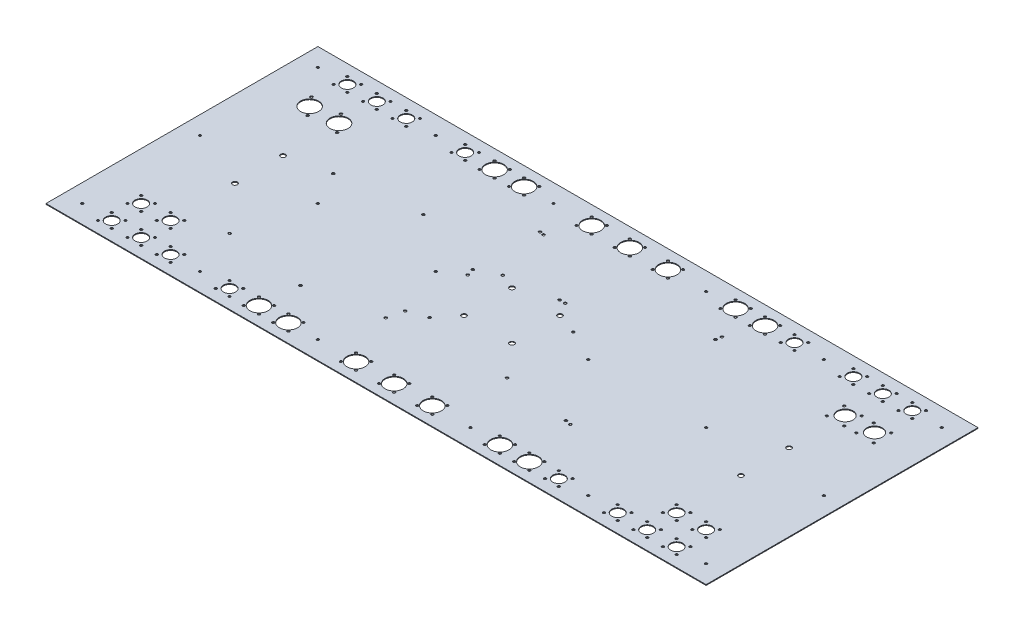
SolidWorks part; units mm, degrees
ref_plane "Front Plane" through (0, 0, 0) normal (0, 0, 1) x (1, 0, 0)
ref_plane "Top Plane" through (0, 0, 0) normal (0, 1, 0) x (1, 0, 0)
ref_plane "Right Plane" through (0, 0, 0) normal (1, 0, 0) x (0, 0, -1)
sketch "main_plate" plane through (0, 0, 0) normal (0, 1, 0) x (1, 0, 0)
  line L1 (-437, 180) -> (437, 180)
  line L2 (-437, 180) -> (-437, -180)
  line L3 (-437, -180) -> (437, -180)
  line L4 (437, 180) -> (437, -180)
  line L5 (-437, 180) -> (437, -180) construction
  line L6 (-437, -180) -> (437, 180) construction
  point P0 (0, 0)
  dimension "D1" = 360
  dimension "D2" = 874
extrude "Boss-Extrude1" add sketch "main_plate" along normal blind 1.016
sketch "main_holes" plane through (0, 1.016, 0) normal (0, 1, 0) x (1, 0, 0)
  line L0 (-437, 180) -> (-437, -180) construction
  line L1 (437, 180) -> (-437, 180) construction
  line L2 (-437, 0) -> (437, 0) construction
  line L3 (437, -180) -> (437, 180) construction
  line L4 (-437, -180) -> (437, -180) construction
  line L5 (0, 180) -> (0, -180) construction
  circle A0 centre (-413, 156) radius 1.6
  circle A3 centre (-335, 31.8059) radius 3.175
  circle A4 centre (-335, -31.8059) radius 3.175
  circle A6 centre (-257, 156) radius 1.6
  circle A7 centre (-101, 156) radius 1.6
  circle A8 centre (-257, 0) radius 1.6
  circle A9 centre (-101, 0) radius 1.6
  circle A10 centre (-257, -156) radius 1.6
  circle A11 centre (-101, -156) radius 1.6
  circle A12 centre (-413, 0) radius 1.6
  circle A13 centre (-413, -156) radius 1.6
  circle A14 centre (-31.75, 31.75) radius 3.175
  circle A15 centre (-31.75, -31.75) radius 3.175
  circle A16 centre (31.75, -31.75) radius 3.175
  circle A17 centre (31.75, 31.75) radius 3.175
  circle A18 centre (413, -156) radius 1.6
  circle A19 centre (413, 0) radius 1.6
  circle A20 centre (101, -156) radius 1.6
  circle A21 centre (257, -156) radius 1.6
  circle A22 centre (101, 0) radius 1.6
  circle A23 centre (257, 0) radius 1.6
  circle A24 centre (101, 156) radius 1.6
  circle A25 centre (257, 156) radius 1.6
  circle A26 centre (335, -31.8059) radius 3.175
  circle A27 centre (335, 31.8059) radius 3.175
  circle A28 centre (413, 156) radius 1.6
  dimension "D3" = 3.2
  dimension "D8" = 6.35
  dimension "D1" = 24
  dimension "D2" = 24
  dimension "D4" = 3
  dimension "D5" = 3
  dimension "D6" = 78
  dimension "D7" = 31.75
  dimension "D9" = 31.75
extrude "Cut-Extrude1" cut sketch "main_holes" against normal through all
sketch "fan" plane through (0, 1.016, 1.016) normal (0, 1, 0) x (1, 0, 0)
  line L0 (-101, 157.016) -> (101, 157.016) construction
  line L1 (-101, -154.984) -> (101, -154.984) construction
  line L2 (101, -154.984) -> (257, -154.984) construction
  line L3 (-257, -154.984) -> (-101, -154.984) construction
  circle A0 centre (-101, -154.984) radius 1.6 construction
  circle A1 centre (101, -154.984) radius 1.6 construction
  circle B0 centre (130, -144.984) radius 1.6
  circle B1 centre (150, -144.984) radius 1.6
  circle B2 centre (150, -164.984) radius 1.6
  circle B3 centre (130, -164.984) radius 1.6
  circle B4 centre (140, -154.984) radius 12
  circle B5 centre (169, -144.984) radius 1.6
  circle B6 centre (189, -144.984) radius 1.6
  circle B7 centre (189, -164.984) radius 1.6
  circle B8 centre (169, -164.984) radius 1.6
  circle B9 centre (179, -154.984) radius 12
  circle B10 centre (-10, -144.984) radius 1.6
  circle B11 centre (10, -144.984) radius 1.6
  circle B12 centre (10, -164.984) radius 1.6
  circle B13 centre (-10, -164.984) radius 1.6
  circle B14 centre (0, -154.984) radius 12
  circle B15 centre (-60.5, -144.984) radius 1.6
  circle B16 centre (-40.5, -144.984) radius 1.6
  circle B17 centre (-40.5, -164.984) radius 1.6
  circle B18 centre (-60.5, -164.984) radius 1.6
  circle B19 centre (-50.5, -154.984) radius 12
  circle B20 centre (40.5, -144.984) radius 1.6
  circle B21 centre (60.5, -144.984) radius 1.6
  circle B22 centre (60.5, -164.984) radius 1.6
  circle B23 centre (40.5, -164.984) radius 1.6
  circle B24 centre (50.5, -154.984) radius 12
  circle B25 centre (-10, 167.016) radius 1.6
  circle B26 centre (10, 167.016) radius 1.6
  circle B27 centre (10, 147.016) radius 1.6
  circle B28 centre (-10, 147.016) radius 1.6
  circle B29 centre (0, 157.016) radius 12
  circle B30 centre (-60.5, 167.016) radius 1.6
  circle B31 centre (-40.5, 167.016) radius 1.6
  circle B32 centre (-40.5, 147.016) radius 1.6
  circle B33 centre (-60.5, 147.016) radius 1.6
  circle B34 centre (-50.5, 157.016) radius 12
  circle B35 centre (40.5, 167.016) radius 1.6
  circle B36 centre (60.5, 167.016) radius 1.6
  circle B37 centre (60.5, 147.016) radius 1.6
  circle B38 centre (40.5, 147.016) radius 1.6
  circle B39 centre (50.5, 157.016) radius 12
  circle B40 centre (-189, -144.984) radius 1.6
  circle B41 centre (-169, -144.984) radius 1.6
  circle B42 centre (-169, -164.984) radius 1.6
  circle B43 centre (-189, -164.984) radius 1.6
  circle B44 centre (-179, -154.984) radius 12
  circle B45 centre (-150, -144.984) radius 1.6
  circle B46 centre (-130, -144.984) radius 1.6
  circle B47 centre (-130, -164.984) radius 1.6
  circle B48 centre (-150, -164.984) radius 1.6
  circle B49 centre (-140, -154.984) radius 12
  circle B50 centre (-189, 167.016) radius 1.6
  circle B51 centre (-169, 167.016) radius 1.6
  circle B52 centre (-169, 147.016) radius 1.6
  circle B53 centre (-189, 147.016) radius 1.6
  circle B54 centre (-179, 157.016) radius 12
  circle B55 centre (-150, 167.016) radius 1.6
  circle B56 centre (-130, 167.016) radius 1.6
  circle B57 centre (-130, 147.016) radius 1.6
  circle B58 centre (-150, 147.016) radius 1.6
  circle B59 centre (-140, 157.016) radius 12
  circle B60 centre (130, 167.016) radius 1.6
  circle B61 centre (150, 167.016) radius 1.6
  circle B62 centre (150, 147.016) radius 1.6
  circle B63 centre (130, 147.016) radius 1.6
  circle B64 centre (140, 157.016) radius 12
  circle B65 centre (169, 167.016) radius 1.6
  circle B66 centre (189, 167.016) radius 1.6
  circle B67 centre (189, 147.016) radius 1.6
  circle B68 centre (169, 147.016) radius 1.6
  circle B69 centre (179, 157.016) radius 12
  dimension "D1" = 39
  dimension "D2" = 202
  dimension "D4" = 39
  dimension "D6" = 39
  dimension "D7" = 39
  dimension "D3" = 50.5
sketch_block_instance "Block2-11"
sketch_block "Block2" parameters "D1"=3.2, "D2"=24, "D3"=10, "D4"=10, "D5"=10, "D6"=10
sketch_block_instance "Block2-12"
sketch_block_instance "Block13-1"
sketch_block "Block13"
sketch_block_instance "Block2-16"
sketch_block_instance "Block2-15"
sketch_block_instance "Block2-17"
sketch_block_instance "Block2-19"
sketch_block_instance "Block13-2"
sketch_block_instance "Block14-1"
sketch_block "Block14"
sketch_block_instance "Block2-18"
sketch_block_instance "Block2-10"
sketch_block_instance "Block14-2"
sketch_block_instance "Block14-3"
extrude "Cut-Extrude2" cut sketch "fan" against normal through all
sketch "ntype" plane through (0, 1.016, 0) normal (0, 1, 0) x (1, 0, 0)
  line L1 (-413, -156) -> (413, -156) construction
  line L2 (413, -156) -> (413, 156) construction
  line L3 (413, 156) -> (-413, 156) construction
  line L4 (-413, 156) -> (-413, -156) construction
  circle A1 centre (-257, 156) radius 1.6 construction
  circle A2 centre (413, 156) radius 1.6 construction
  circle A3 centre (-257, -156) radius 1.6 construction
  circle A4 centre (257, -156) radius 1.6 construction
  circle A5 centre (257, 156) radius 1.6 construction
  circle B0 centre (-218, 156) radius 8
  circle B1 centre (-227.1, 165.1) radius 1.6
  circle B2 centre (-208.9, 165.1) radius 1.6
  circle B3 centre (-208.9, 146.9) radius 1.6
  circle B4 centre (-227.1, 146.9) radius 1.6
  circle B5 centre (218, 156) radius 8
  circle B6 centre (208.9, 165.1) radius 1.6
  circle B7 centre (227.1, 165.1) radius 1.6
  circle B8 centre (227.1, 146.9) radius 1.6
  circle B9 centre (208.9, 146.9) radius 1.6
  circle B10 centre (-218, -156) radius 8
  circle B11 centre (-227.1, -146.9) radius 1.6
  circle B12 centre (-208.9, -146.9) radius 1.6
  circle B13 centre (-208.9, -165.1) radius 1.6
  circle B14 centre (-227.1, -165.1) radius 1.6
  circle B15 centre (218, -156) radius 8
  circle B16 centre (208.9, -146.9) radius 1.6
  circle B17 centre (227.1, -146.9) radius 1.6
  circle B18 centre (227.1, -165.1) radius 1.6
  circle B19 centre (208.9, -165.1) radius 1.6
  circle B20 centre (-374, 156) radius 8
  circle B21 centre (-383.1, 165.1) radius 1.6
  circle B22 centre (-364.9, 165.1) radius 1.6
  circle B23 centre (-364.9, 146.9) radius 1.6
  circle B24 centre (-383.1, 146.9) radius 1.6
  circle B25 centre (-296, 156) radius 8
  circle B26 centre (-305.1, 165.1) radius 1.6
  circle B27 centre (-286.9, 165.1) radius 1.6
  circle B28 centre (-286.9, 146.9) radius 1.6
  circle B29 centre (-305.1, 146.9) radius 1.6
  circle B30 centre (-335, 156) radius 8
  circle B31 centre (-344.1, 165.1) radius 1.6
  circle B32 centre (-325.9, 165.1) radius 1.6
  circle B33 centre (-325.9, 146.9) radius 1.6
  circle B34 centre (-344.1, 146.9) radius 1.6
  circle B35 centre (296, -156) radius 8
  circle B36 centre (286.9, -146.9) radius 1.6
  circle B37 centre (305.1, -146.9) radius 1.6
  circle B38 centre (305.1, -165.1) radius 1.6
  circle B39 centre (286.9, -165.1) radius 1.6
  circle B40 centre (374, -156) radius 8
  circle B41 centre (364.9, -146.9) radius 1.6
  circle B42 centre (383.1, -146.9) radius 1.6
  circle B43 centre (383.1, -165.1) radius 1.6
  circle B44 centre (364.9, -165.1) radius 1.6
  circle B45 centre (335, -156) radius 8
  circle B46 centre (325.9, -146.9) radius 1.6
  circle B47 centre (344.1, -146.9) radius 1.6
  circle B48 centre (344.1, -165.1) radius 1.6
  circle B49 centre (325.9, -165.1) radius 1.6
  circle B50 centre (296, 156) radius 8
  circle B51 centre (286.9, 165.1) radius 1.6
  circle B52 centre (305.1, 165.1) radius 1.6
  circle B53 centre (305.1, 146.9) radius 1.6
  circle B54 centre (286.9, 146.9) radius 1.6
  circle B55 centre (374, 156) radius 8
  circle B56 centre (364.9, 165.1) radius 1.6
  circle B57 centre (383.1, 165.1) radius 1.6
  circle B58 centre (383.1, 146.9) radius 1.6
  circle B59 centre (364.9, 146.9) radius 1.6
  circle B60 centre (335, 156) radius 8
  circle B61 centre (325.9, 165.1) radius 1.6
  circle B62 centre (344.1, 165.1) radius 1.6
  circle B63 centre (344.1, 146.9) radius 1.6
  circle B64 centre (325.9, 146.9) radius 1.6
  circle B65 centre (-374, -156) radius 8
  circle B66 centre (-383.1, -146.9) radius 1.6
  circle B67 centre (-364.9, -146.9) radius 1.6
  circle B68 centre (-364.9, -165.1) radius 1.6
  circle B69 centre (-383.1, -165.1) radius 1.6
  circle B70 centre (-296, -156) radius 8
  circle B71 centre (-305.1, -146.9) radius 1.6
  circle B72 centre (-286.9, -146.9) radius 1.6
  circle B73 centre (-286.9, -165.1) radius 1.6
  circle B74 centre (-305.1, -165.1) radius 1.6
  circle B75 centre (-335, -156) radius 8
  circle B76 centre (-344.1, -146.9) radius 1.6
  circle B77 centre (-325.9, -146.9) radius 1.6
  circle B78 centre (-325.9, -165.1) radius 1.6
  circle B79 centre (-344.1, -165.1) radius 1.6
  circle B80 centre (-335, -117) radius 8
  circle B81 centre (-344.1, -107.9) radius 1.6
  circle B82 centre (-325.9, -107.9) radius 1.6
  circle B83 centre (-325.9, -126.1) radius 1.6
  circle B84 centre (-344.1, -126.1) radius 1.6
  circle B85 centre (-374, -117) radius 8
  circle B86 centre (-383.1, -107.9) radius 1.6
  circle B87 centre (-364.9, -107.9) radius 1.6
  circle B88 centre (-364.9, -126.1) radius 1.6
  circle B89 centre (-383.1, -126.1) radius 1.6
  circle B90 centre (374, -117) radius 8
  circle B91 centre (364.9, -107.9) radius 1.6
  circle B92 centre (383.1, -107.9) radius 1.6
  circle B93 centre (383.1, -126.1) radius 1.6
  circle B94 centre (364.9, -126.1) radius 1.6
  circle B95 centre (335, -117) radius 8
  circle B96 centre (325.9, -107.9) radius 1.6
  circle B97 centre (344.1, -107.9) radius 1.6
  circle B98 centre (344.1, -126.1) radius 1.6
  circle B99 centre (325.9, -126.1) radius 1.6
  dimension "D1" = 156
  dimension "D2" = 39
  dimension "D4" = 39
  dimension "D3" = 39
  dimension "D5" = 39
  dimension "D6" = 39
  dimension "D7" = 39
  dimension "D8" = 39
  dimension "D9" = 39
  dimension "D10" = 39
  dimension "D11" = 39
sketch_block_instance "Block3-10"
sketch_block "Block3" parameters "D1"=3.2, "D2"=16, "D3"=9.1, "D4"=9.1, "D5"=9.1, "D6"=9.1
sketch_block_instance "Block3-16"
sketch_block_instance "Block3-17"
sketch_block_instance "Block3-18"
sketch_block_instance "Block3-19"
sketch_block_instance "Block11-1"
sketch_block "Block11"
sketch_block_instance "Block3-24"
sketch_block_instance "Block3-23"
sketch_block_instance "Block3-21"
sketch_block_instance "Block11-2"
sketch_block_instance "Block11-3"
sketch_block_instance "Block11-4"
sketch_block_instance "Block12-1"
sketch_block "Block12"
sketch_block_instance "Block3-27"
sketch_block_instance "Block3-28"
sketch_block_instance "Block12-2"
extrude "Cut-Extrude3" cut sketch "ntype" against normal through all
sketch "ethernet" plane through (0, 1.016, 0) normal (0, 1, 0) x (1, 0, 0)
  circle A1 centre (-413, 156) radius 1.6 construction
  circle B0 centre (-374, 106) radius 12
  circle B1 centre (-383.5, 118) radius 1.755
  circle B2 centre (-364.5, 94) radius 1.755
  circle B3 centre (-335, 106) radius 12
  circle B4 centre (-344.5, 118) radius 1.755
  circle B5 centre (-325.5, 94) radius 1.755
  dimension "D1" = 39
  dimension "D2" = 2
  dimension "D3" = 50
sketch_block_instance "Block9-1"
sketch_block "Block9" parameters "D1"=24, "D2"=3.51, "D3"=19, "D4"=24, "D5"=9.5, "D6"=12
sketch_block_instance "Block9-3"
extrude "Cut-Extrude6" cut sketch "ethernet" against normal blind 10
sketch "power" plane through (0, 1.016, 0) normal (0, 1, 0) x (1, 0, 0)
  circle A0 centre (413, 156) radius 1.6 construction
  circle B0 centre (374, 106) radius 10.4521
  circle B1 centre (362.4938, 116.4521) radius 1.5875
  circle B2 centre (385.5062, 116.4521) radius 1.5875
  circle B3 centre (385.5062, 93.4397) radius 1.5875
  circle B4 centre (362.4938, 93.4397) radius 1.5875
  circle B5 centre (335, 106) radius 10.4521
  circle B6 centre (323.4938, 116.4521) radius 1.5875
  circle B7 centre (346.5062, 116.4521) radius 1.5875
  circle B8 centre (346.5062, 93.4397) radius 1.5875
  circle B9 centre (323.4938, 93.4397) radius 1.5875
  dimension "D1" = 39
  dimension "D2" = 50
  dimension "D3" = 2
sketch_block_instance "Block10-1"
sketch_block "Block10" parameters "D1"=20.9042, "D2"=3.175, "D3"=10.4521, "D4"=23.0124, "D5"=11.5062
sketch_block_instance "Block10-2"
extrude "Cut-Extrude7" cut sketch "power" against normal blind 10
sketch "ads9+eval" plane through (0, 1.016, -2.032) normal (0, 1, 0) x (-1, 0, 0)
  line L0 (-169.9282, 95.2236) -> (89.7818, 95.2236) construction
  line L1 (-169.9282, 95.2236) -> (-169.9282, -120.6764) construction
  line L2 (-169.9282, -120.6764) -> (89.7818, -120.6764) construction
  line L3 (89.7818, 95.2236) -> (89.7818, -120.6764) construction
  line L4 (-169.9282, 95.2236) -> (89.7818, -120.6764) construction
  line L5 (-169.9282, -120.6764) -> (89.7818, 95.2236) construction
  line L6 (60.9654, 26.3306) -> (297.6934, 26.2036) construction
  line L7 (79.7614, 122.7236) -> (297.6934, 122.7236) construction
  line L8 (79.7614, 122.7236) -> (79.7614, 61.5096) construction
  line L9 (79.7614, -70.3164) -> (297.6934, -70.3164) construction
  line L10 (297.6934, 122.7236) -> (297.6934, -70.3164) construction
  line L11 (79.7614, 122.7236) -> (297.6934, -70.3164) construction
  line L12 (79.7614, -70.3164) -> (297.6934, 122.7236) construction
  line L13 (60.9654, 61.5096) -> (79.7614, 61.5096) construction
  line L14 (60.9654, 61.5096) -> (60.9654, -8.8484) construction
  line L15 (60.9654, -8.8484) -> (79.7614, -8.8484) construction
  line L16 (79.7614, -70.3164) -> (79.7614, -8.8484) construction
  circle A0 centre (-163.4482, 88.2036) radius 1.75
  circle A1 centre (-156.2082, 86.8836) radius 1.75
  circle A2 centre (-162.1882, -105.2764) radius 1.75
  circle A3 centre (-163.4582, -112.4564) radius 1.75
  circle A4 centre (-21.2182, -47.3664) radius 1.75
  circle A5 centre (-13.5982, -47.3664) radius 1.75
  circle A6 centre (52.2618, -38.1164) radius 1.75
  circle A7 centre (-59.4982, -19.7364) radius 1.75
  circle A8 centre (78.6518, -24.8264) radius 1.75
  circle A9 centre (75.9418, -15.3564) radius 1.75
  circle A10 centre (71.7418, -111.4964) radius 1.75
  circle A11 centre (77.3842, -112.4564) radius 1.75
  circle A12 centre (52.2718, 58.9136) radius 1.75
  circle A13 centre (76.1018, 67.4436) radius 1.75
  circle A14 centre (81.0218, 88.2036) radius 1.75
  circle A15 centre (-68.1982, 76.8136) radius 1.75
  circle A16 centre (174.4714, 107.5497) radius 1.75
  circle A17 centre (281.1514, 94.7924) radius 1.75
  circle A18 centre (281.0779, -42.3675) radius 1.75
  circle A19 centre (174.3842, -55.0103) radius 1.75
  point P0 (-40.0732, -12.7264)
  point P37 (188.7274, 26.2036)
  dimension "D6" = 3.5
  dimension "D44" = 3.5
  dimension "D1" = 27.5
  dimension "D2" = 97
  dimension "D3" = 100.3781
  dimension "D4" = 215.9
  dimension "D5" = 259.71
  dimension "D7" = 6.48
  dimension "D8" = 7.24
  dimension "D9" = 111
  dimension "D10" = 103.38
  dimension "D11" = 18.04
  dimension "D12" = 12.3976
  dimension "D13" = 37.52
  dimension "D14" = 11.13
  dimension "D15" = 13.84
  dimension "D16" = 110.43
  dimension "D17" = 101.73
  dimension "D18" = 7.74
  dimension "D19" = 6.47
  dimension "D20" = 37.51
  dimension "D21" = 13.68
  dimension "D22" = 8.76
  dimension "D23" = 15.4
  dimension "D24" = 8.22
  dimension "D25" = 100.94
  dimension "D26" = 7.02
  dimension "D27" = 8.34
  dimension "D28" = 18.41
  dimension "D29" = 36.31
  dimension "D30" = 27.78
  dimension "D31" = 7.02
  dimension "D32" = 8.22
  dimension "D33" = 9.18
  dimension "D34" = 73.31
  dimension "D35" = 73.31
  dimension "D36" = 82.56
  dimension "D37" = 105.32
  dimension "D38" = 95.85
  dimension "D39" = 217.932
  dimension "D40" = 70.358
  dimension "D41" = 61.468
  dimension "D42" = 193.04
  dimension "D43" = 18.796
  dimension "D45" = 81.28
  dimension "D46" = 68.58
  dimension "D47" = 94.71
  dimension "D48" = 106.68
extrude "Cut-Extrude8" cut sketch "ads9+eval" against normal blind 10
